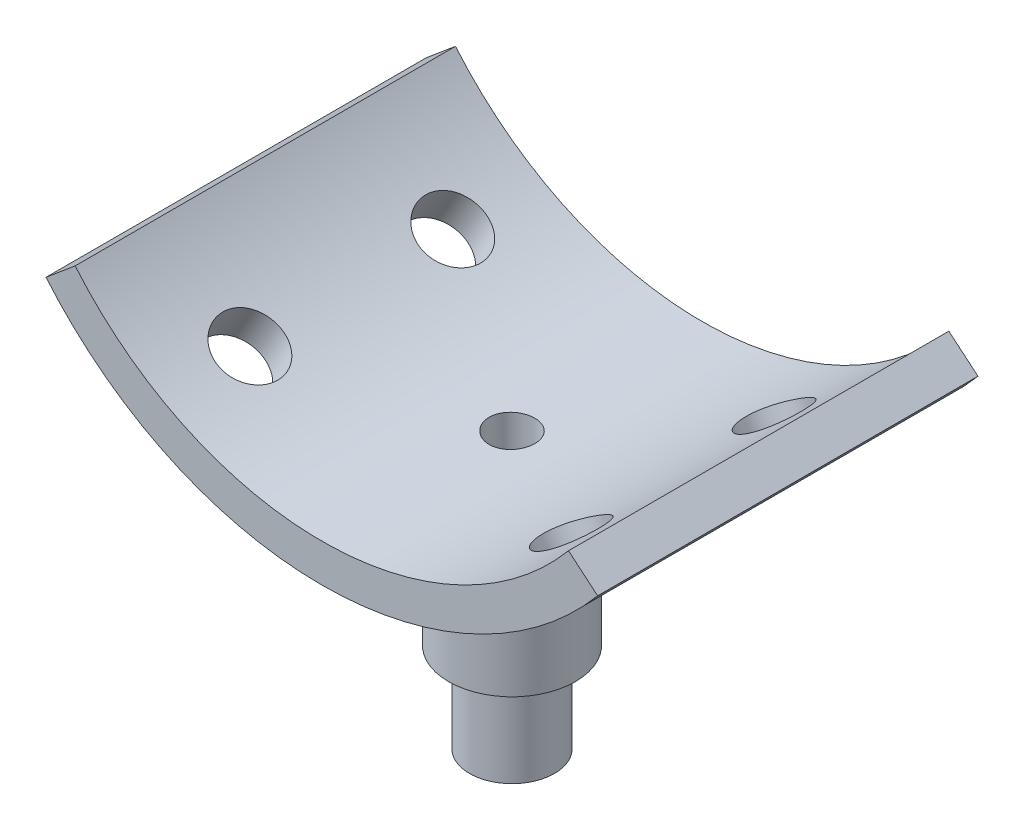
SolidWorks part; units mm, degrees
ref_plane "Front Plane" through (0, 0, 0) normal (0, 0, 1) x (1, 0, 0)
ref_plane "Top Plane" through (0, 0, 0) normal (0, 1, 0) x (1, 0, 0)
ref_plane "Right Plane" through (0, 0, 0) normal (1, 0, 0) x (0, 0, -1)
sketch "Sketch1" plane through (0, 0, 0) normal (0, 0, 1) x (1, 0, 0)
  line L0 (0, 31.2519) -> (0, -31.2519) construction
  line L1 (0, 0) -> (-21.7557, -18.2552) construction
  line L2 (0, 0) -> (21.7557, -18.2552) construction
  line L3 (21.7557, -18.2552) -> (19.4575, -16.3268)
  line L4 (-21.7557, -18.2552) -> (-19.4575, -16.3268)
  arc A0 (-19.4575, -16.3268) -> (19.4575, -16.3268) centre (0, 0) ccw
  arc A1 (-21.7557, -18.2552) -> (21.7557, -18.2552) centre (0, 0) ccw
  circle A2 centre (0, 0) radius 28.4 construction
  circle A3 centre (0, 0) radius 25.4 construction
  point P8 (0, 0)
  dimension "D1" = 50.8
  dimension "D3" = 50
  dimension "D2" = 3
extrude "Boss-Extrude1" add sketch "Sketch1" along normal mid plane 30
ref_plane "Plane1" through (0, -40, 0) normal (0, 1, 0) x (1, 0, 0)
sketch "Sketch2" plane through (0, -40, 0) normal (0, 1, 0) x (1, 0, 0)
  circle A0 centre (0, 0) radius 5
  dimension "D1" = 10
extrude "Boss-Extrude2" add sketch "Sketch2" along normal up to surface (11.6 mm away) up to face at (0, -23.3276, 0)
sketch "Sketch5" plane through (0, 0, 0) normal (0, 0, 1) x (1, 0, 0)
  line L0 (0, 0) -> (14.2, -24.5951) construction
  line L1 (0, 14.0723) -> (0, -38.9472) construction
  line L2 (0, 0) -> (-14.2, -24.5951) construction
  arc A0 (-21.7557, -18.2552) -> (21.7557, -18.2552) centre (0, 0) ccw construction
  dimension "D1" = 30
ref_plane "Plane3" through (14.2, -24.5951, 0) normal (0.5, -0.866, 0) x (-0.866, -0.5, 0)
sketch "Sketch13" plane through (14.2, -24.5951, 0) normal (0.5, -0.866, 0) x (-0.866, -0.5, 0)
  line L0 (-17.4465, 0) -> (25.4678, 0) construction
  circle A1 centre (0, 8) radius 2.5
  circle A2 centre (0, -8) radius 2.5
  dimension "D1" = 5
  dimension "D2" = 8
extrude "Cut-Extrude2" cut sketch "Sketch13" against normal through all
mirror "Mirror1" about plane through (0, 0, 0) normal (1, 0, 0) of "Cut-Extrude2"
sketch "Sketch14" plane through (0, -40, 0) normal (0, -1, 0) x (1, 0, 0)
  circle A0 centre (0, 0) radius 3.35
  dimension "D1" = 6.7
extrude "Boss-Extrude4" add sketch "Sketch14" along normal blind 7.1
sketch "Sketch4" plane through (0, -40, 0) normal (0, -1, 0) x (1, 0, 0)
  line L0 (-6.6, 0) -> (6.6, 0) construction
  line L5 (-6.6, 0.8) -> (-4.9356, 0.8)
  line L6 (-6.6, 0.8) -> (-6.6, -0.8)
  line L7 (-6.6, -0.8) -> (-4.9356, -0.8)
  line L8 (6.6, 0.8) -> (6.6, -0.8)
  line L9 (0, 12.2903) -> (0, -12.2903) construction
  line L10 (4.9356, 0.8) -> (6.6, 0.8)
  line L11 (4.9356, -0.8) -> (6.6, -0.8)
  circle A0 centre (0, 0) radius 5 construction
  arc A1 (-4.9356, 0.8) -> (-4.9356, -0.8) centre (0, 0) ccw
  arc A2 (4.9356, -0.8) -> (4.9356, 0.8) centre (0, 0) ccw
  point P10 (0, 0)
  point P11 (0, 0)
  point P12 (6.6, 0)
  point P20 (5, 0)
  dimension "D1" = 1.6
  dimension "D2" = 1.6
sketch "Sketch15" plane through (0, -47.1, 0) normal (0, -1, 0) x (1, 0, 0)
  circle A0 centre (0, 0) radius 1.8
  dimension "D1" = 3.6
extrude "Cut-Extrude3" cut sketch "Sketch15" against normal through all
